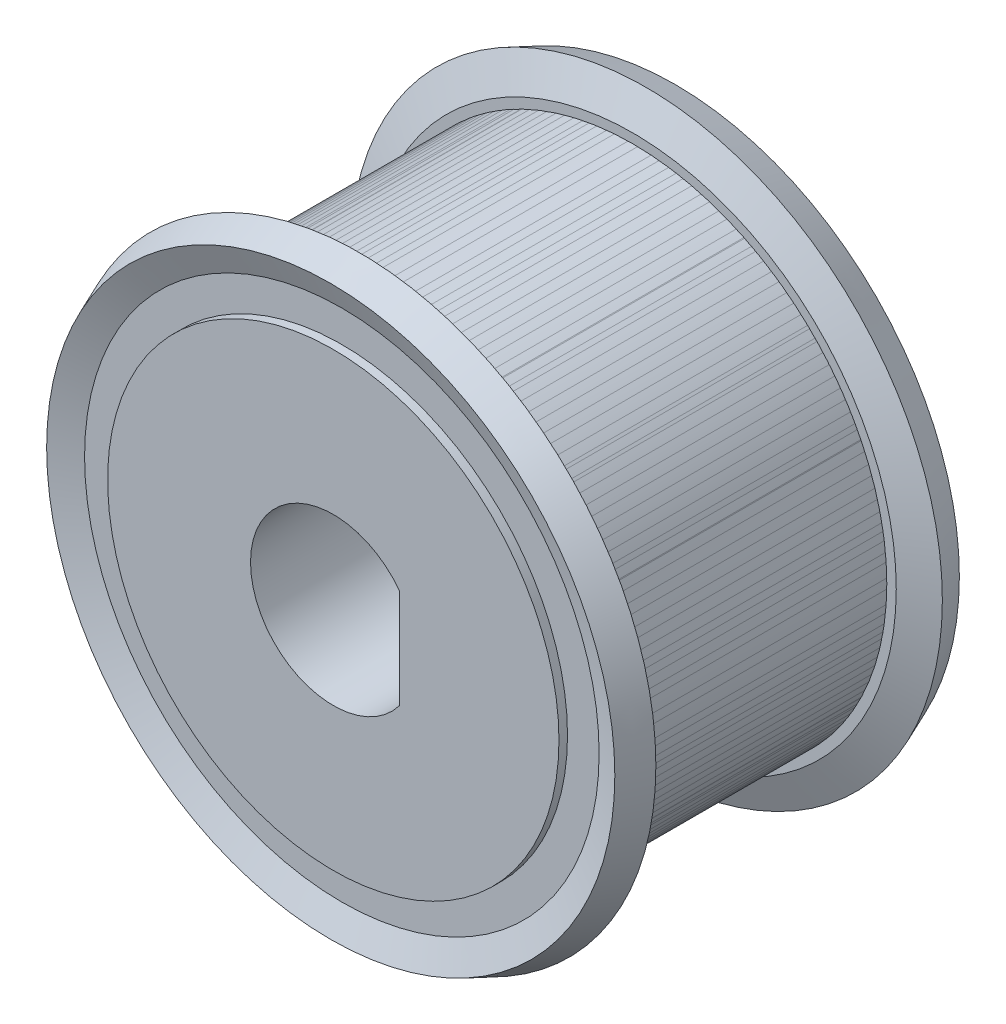
SolidWorks part; units mm, degrees
note: '?' marks a value the reader was unsure of.
material "6061 合金"
ref_plane "前视基准面" through (0, 0, 0) normal (0, 0, 1) x (1, 0, 0)
ref_plane "上视基准面" through (0, 0, 0) normal (0, 1, 0) x (1, 0, 0)
ref_plane "右视基准面" through (0, 0, 0) normal (1, 0, 0) x (0, 0, -1)
ref_axis "基准轴1" through (0, 0, 55) along (0, 0, -1)?
sketch "SketchRevolveGearBelt01" plane through (0, 0, 0) normal (1, 0, 0) x (0, 0, -1)
  line L0 (0, 0) -> (1, 0) construction
  line L1 (10.2489, 0) -> (10.2489, 13.6295)
  line L2 (10.2489, 13.6295) -> (9.7333, 13.6295)
  line L3 (9.7333, 13.6295) -> (9.7333, 15.5381)
  line L4 (9.7333, 15.5381) -> (10.4042, 17.1579)
  line L5 (10.4042, 17.1579) -> (8.6513, 17.884)
  line L6 (8.6513, 17.884) -> (7.8359, 15.9155)
  line L7 (7.8359, 15.9155) -> (7.8359, 15.344)
  line L8 (7.8359, 15.344) -> (-7.8359, 15.344)
  line L9 (-7.8359, 15.344) -> (-7.8359, 15.9155)
  line L10 (-7.8359, 15.9155) -> (-8.6513, 17.884)
  line L11 (-8.6513, 17.884) -> (-10.4042, 17.1579)
  line L12 (-10.4042, 17.1579) -> (-9.7333, 15.5381)
  line L13 (-9.7333, 15.5381) -> (-9.7333, 13.6295)
  line L14 (-9.7333, 13.6295) -> (-10.2489, 13.6295)
  line L15 (-10.2489, 13.6295) -> (-10.2489, 0)
  line L16 (-10.2489, 0) -> (10.2489, 0)
  dimension "GearBeltFlange1OutsideLength" = 1.9086
  dimension "GearBeltFlange1X" = 0.6709
  dimension "GearBeltFlange1Y" = 1.6198
  dimension "GearBeltFlangeThickness" = 1.8974
  dimension "GearBeltFlangeInside" = 0.5715
  dimension "GearBeltOutsideDiameter" = 15.344
  dimension "GearBeltFlange2X" = 0.6709
revolve "GearBelt01" add sketch "SketchRevolveGearBelt01" angle 360 about L0
sketch "SketchToothGearBelt01" plane through (0, 0, 0) normal (0, 0, 1) x (1, 0, 0)
  arc A0 (15.1892, 2.17) -> (15.1892, -2.17) centre (0, 0) cw
  spline S0 degree 3 poles (15.1892, -2.17) (15.1933, -2.1413) (15.1958, -2.0978) (15.1916, -2.0399) (15.1848, -1.997) (15.1743, -1.9547) (15.1603, -1.9136) (15.1428, -1.8738) (15.1219, -1.8356) (15.0979, -1.7993) (15.0709, -1.7653) (15.041, -1.7336) (15.0086, -1.7046) (14.9738, -1.6785) (14.9369, -1.6555) (14.8981, -1.6357) (14.8578, -1.6193) (14.8163, -1.6064) (14.7738, -1.5971) (14.7307, -1.5914) (14.6736, -1.5894) (14.5978, -1.5908) (14.5033, -1.5873) (14.4043, -1.5753) (14.3065, -1.5557) (14.2106, -1.5285) (14.1171, -1.4939) (14.0266, -1.452) (13.9397, -1.4032) (13.8569, -1.3477) (13.7786, -1.2859) (13.7055, -1.2181) (13.6379, -1.1449) (13.5762, -1.0665) (13.5209, -0.9836) (13.4722, -0.8965) (13.4305, -0.806) (13.396, -0.7124) (13.369, -0.6164) (13.3496, -0.5186) (13.3376, -0.4196) (13.3342, -0.2999) (13.3356, -0.16) (13.3351, 0) (13.3356, 0.16) (13.3342, 0.2999) (13.3376, 0.4196) (13.3496, 0.5186) (13.369, 0.6164) (13.396, 0.7124) (13.4305, 0.806) (13.4722, 0.8965) (13.5209, 0.9836) (13.5762, 1.0665) (13.6379, 1.1449) (13.7055, 1.2181) (13.7786, 1.2859) (13.8569, 1.3477) (13.9397, 1.4032) (14.0266, 1.452) (14.1171, 1.4939) (14.2106, 1.5285) (14.3065, 1.5557) (14.4043, 1.5753) (14.5033, 1.5873) (14.5978, 1.5908) (14.6736, 1.5894) (14.7307, 1.5914) (14.7738, 1.5971) (14.8163, 1.6064) (14.8578, 1.6193) (14.8981, 1.6357) (14.9369, 1.6555) (14.9738, 1.6785) (15.0086, 1.7046) (15.041, 1.7336) (15.0709, 1.7653) (15.0979, 1.7993) (15.1219, 1.8356) (15.1428, 1.8738) (15.1603, 1.9136) (15.1743, 1.9547) (15.1848, 1.997) (15.1916, 2.0399) (15.1958, 2.0978) (15.1933, 2.1413) (15.1892, 2.17) knots 0 0 0 0 0.013305 0.019957 0.026609 0.033261 0.039914 0.046566 0.053218 0.059871 0.066523 0.073175 0.079828 0.08648 0.093132 0.099784 0.106437 0.113089 0.119741 0.126394 0.133046 0.145958 0.16121 0.176462 0.191714 0.206966 0.222218 0.23747 0.252722 0.267974 0.283226 0.298478 0.31373 0.328983 0.344235 0.359487 0.374739 0.389991 0.405243 0.420495 0.435747 0.450999 0.4755 0.5 0.5245 0.549001 0.564253 0.579505 0.594757 0.610009 0.625261 0.640513 0.655765 0.671017 0.68627 0.701522 0.716774 0.732026 0.747278 0.76253 0.777782 0.793034 0.808286 0.823538 0.83879 0.854042 0.866954 0.873606 0.880259 0.886911 0.893563 0.900216 0.906868 0.91352 0.920172 0.926825 0.933477 0.940129 0.946782 0.953434 0.960086 0.966739 0.973391 0.980043 0.986695 1 1 1 1
extrude "ToothExtrudeCutGearBelt01" cut sketch "SketchToothGearBelt01" against normal blind 7.8359 and the other way blind 7.8359
pattern_circular "PatternGearBelt01" count 20 every 18 about axis through (0, 0, 55) along (0, 0, -1) of "ToothExtrudeCutGearBelt01"
sketch "AuxiliarySketchGearBelt01" plane through (0, 0, 0) normal (0, 0, 1) x (1, 0, 0)
  circle A0 centre (0, 0) radius 15.9155 construction
  dimension "PitchDiameter" = 31.831
sketch "草图5" plane through (0, 0, 10.2489) normal (0, 0, 1) x (1, 0, 0)
  line L0 (4, 3) -> (4, -3)
  circle A0 centre (0, 0) radius 5
  dimension "D1" = 10
  dimension "D2" = 4
extrude "切除-拉伸2" cut sketch "草图5" against normal through all and the other way through all contours L0 A0
sketch "草图8" [suppressed] plane through (4, 0, 0) normal (-1, 0, 0) x (0, 0, 1)
  point P0 (0, 0)
  point P1 (0, 0)
hole_wizard "M3 螺纹孔1" [suppressed] positions "3D草图1" profile "草图9" tap size "M3" standard "GB"
sketch3d "3D草图1" [suppressed]
  point P0 (4, 0, 0)
sketch "草图9" plane through (4, 0, 0) normal (0, 1, 0) x (0, 0, 1)
  line L0 (0, 0) -> (0, 13.884)
  line L1 (0, 13.884) -> (1.25, 13.884)
  line L2 (1.25, 13.884) -> (1.25, 0)
  line L5 (1.25, 0) -> (0, 0)
  line L11 (0, -6.35) -> (0, 107.95) construction
  dimension "螺纹线主直径" = 2.5
  dimension "通孔螺纹孔钻头深度" = 13.884
